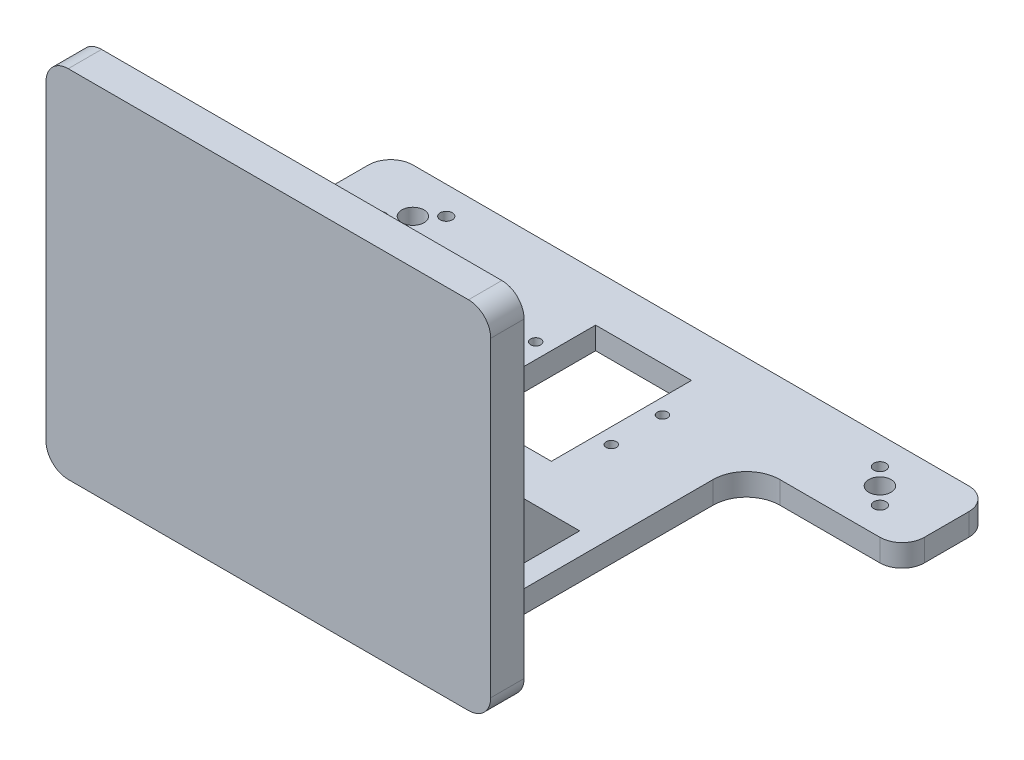
SolidWorks part; units mm, degrees
ref_plane "Vorne" through (0, 0, 0) normal (0, 0, 1) x (1, 0, 0)
ref_plane "Oben" through (0, 0, 0) normal (0, 1, 0) x (1, 0, 0)
ref_plane "Rechts" through (0, 0, 0) normal (1, 0, 0) x (0, 0, -1)
ref_plane "E_Boden" through (0, 1, 0) normal (0, 1, 0) x (1, 0, 0)
sketch "Skizze1" plane through (0, 0, 0) normal (0, 1, 0) x (1, 0, 0)
  line L0 (0, -133.037) -> (0, 127.1868) construction
  line L1 (-165.4867, 0) -> (188.3198, 0) construction
  line L2 (-125, 95) -> (125, 95)
  line L3 (-135, 85) -> (-135, 65)
  line L8 (-125, 55) -> (-80, 55)
  line L9 (-65, 40) -> (-65, -65)
  line L10 (-80, -80) -> (-90, -80)
  line L12 (-80, -95) -> (80, -95)
  line L14 (80, -80) -> (90, -80)
  line L15 (65, 40) -> (65, -65)
  line L16 (125, 55) -> (80, 55)
  line L17 (135, 85) -> (135, 65)
  line L18 (0, 75) -> (-166.9097, 75) construction
  line L19 (0, 82.5) -> (-150.2601, 82.5) construction
  line L20 (0, 67.5) -> (-143.7021, 67.5) construction
  line L21 (-112.5, 67.5) -> (-112.5, 109.8946) construction
  line L22 (-97.5, 82.5) -> (-97.5, 110.5565) construction
  line L23 (-105, 75) -> (-105, 35) construction
  line L24 (-105, 35) -> (-105, 140.5126) construction
  line L25 (-21.55, 73.71) -> (21.55, 73.71)
  line L26 (21.55, 73.71) -> (21.55, 10.71)
  line L27 (21.55, 10.71) -> (-21.55, 10.71)
  line L28 (-21.55, 10.71) -> (-21.55, 73.71)
  line L29 (0, 42.21) -> (-56.3168, 42.21) construction
  line L30 (-56.3168, 42.21) -> (55.721, 42.21) construction
  line L32 (-100, -95) -> (-80, -95)
  line L33 (80, -95) -> (100, -95)
  line L35 (-90, -80) -> (-100, -80)
  line L37 (90, -80) -> (100, -80)
  line L39 (-100, -80) -> (-100, -95)
  line L40 (100, -80) -> (100, -95)
  line L41 (-38.4535, 53.71) -> (31.8987, 53.71) construction
  arc A0 (65, 40) -> (80, 55) centre (80, 40) cw
  arc A1 (80, -80) -> (65, -65) centre (80, -65) cw
  arc A2 (-65, -65) -> (-80, -80) centre (-80, -65) cw
  arc A3 (-80, 55) -> (-65, 40) centre (-80, 40) cw
  arc A8 (-135, 65) -> (-125, 55) centre (-125, 65) ccw
  arc A9 (125, 55) -> (135, 65) centre (125, 65) ccw
  arc A10 (135, 85) -> (125, 95) centre (125, 85) ccw
  arc A11 (-125, 95) -> (-135, 85) centre (-125, 85) ccw
  circle A12 centre (-105, 75) radius 5
  circle A13 centre (105, 75) radius 5
  circle A14 centre (-97.5, 82.5) radius 2.75
  circle A15 centre (-112.5, 67.5) radius 2.75
  circle A16 centre (97.5, 82.5) radius 2.75
  circle A17 centre (112.5, 67.5) radius 2.75
  circle A18 centre (-28.5, 53.71) radius 2.3
  circle A19 centre (-28.5, 30.71) radius 2.3
  circle A20 centre (28.5, 30.71) radius 2.3
  circle A21 centre (28.5, 53.71) radius 2.3
  point P15 (0, -95)
  point P16 (0, 95)
  point P22 (65, 55)
  point P25 (65, -80)
  point P28 (-65, -80)
  point P31 (-65, 55)
  point P34 (100, -80)
  point P37 (100, -95)
  point P40 (-100, -95)
  point P43 (-100, -80)
  point P46 (-135, 55)
  point P49 (135, 55)
  point P52 (135, 95)
  point P55 (-135, 95)
  point P77 (0, 42.21)
  dimension "D7" = 15
  dimension "D8" = 10
  dimension "D9" = 10
  dimension "D13" = 5.5
  dimension "D14" = 5.5
  dimension "D20" = 4.6
  dimension "D21" = 20
  dimension "D1" = 270
  dimension "D2" = 40
  dimension "D3" = 150
  dimension "D4" = 200
  dimension "D5" = 130
  dimension "D6" = 15
  dimension "D10" = 210
  dimension "D11" = 15
  dimension "D12" = 7.5
  dimension "D15" = 15
  dimension "D16" = 7.5
  dimension "D17" = 32.79
  dimension "D18" = 43.1
  dimension "D19" = 63
  dimension "D22" = 28.5
extrude "Aufsatz-Linear austragen1" add sketch "Skizze1" along normal blind 10
sketch "Skizze2" plane through (0, 10, 0) normal (0, 1, 0) x (1, 0, 0)
sketch "Skizze3" plane through (0, 10, 0) normal (0, 1, 0) x (1, 0, 0)
  line L1 (-100, -80) -> (100, -80)
  line L2 (-100, -80) -> (-100, -95)
  line L3 (-100, -95) -> (100, -95)
  line L4 (100, -80) -> (100, -95)
extrude "Aufsatz-Linear austragen2" add sketch "Skizze3" along normal blind 150
fillet "Verrundung1" radius 10 4 edges at (100, 0, 87.5) (-100, 0, 87.5) (-100, 160, 87.5) (100, 160, 87.5)
ref_plane "Ebene1" through (-50, 0, 0) normal (-1, 0, 0) x (0, 0, 1)
sketch "Skizze5" plane through (-50, 0, 0) normal (-1, 0, 0) x (0, 0, 1)
  line L0 (10, 10) -> (80, 80)
  line L1 (-40, 10) -> (65, 10) construction
  line L2 (80, 150) -> (80, 10) construction
  line L3 (80, 80) -> (80, 10)
  line L4 (80, 10) -> (10, 10)
  dimension "D1" = 70
  dimension "D2" = 70
extrude "Aufsatz-Linear austragen3" add sketch "Skizze5" against normal blind 10
ref_plane "Ebene2" through (55, 0, 0) normal (1, 0, 0) x (0, 0, -1)
sketch "Skizze6" plane through (55, 0, 0) normal (1, 0, 0) x (0, 0, -1)
  line L0 (-10, 10) -> (-80, 80)
  line L1 (-80, 150) -> (-80, 10) construction
  line L2 (-80, 80) -> (-80, 10)
  line L3 (-80, 10) -> (-10, 10)
extrude "Aufsatz-Linear austragen4" add sketch "Skizze6" against normal blind 10
sketch "Skizze7" plane through (0, 10, 0) normal (0, 1, 0) x (1, 0, 0)
  line L0 (0, 73.71) -> (0, 10.71) construction
  line L1 (21.55, 73.71) -> (-21.55, 73.71) construction
  line L2 (-21.55, 10.71) -> (21.55, 10.71) construction
  line L3 (-21.55, 42.21) -> (21.55, 42.21) construction
  line L4 (-21.55, 73.71) -> (-21.55, 10.71) construction
  line L5 (21.55, 10.71) -> (21.55, 73.71) construction
  line L6 (-105, 58) -> (0, 25.21)
  line L7 (-105, 92) -> (4.9584, 58.4708)
  circle A0 centre (-105, 75) radius 17
  circle A1 centre (0, 42.21) radius 17
  dimension "D1" = 34
  dimension "D2" = 34
